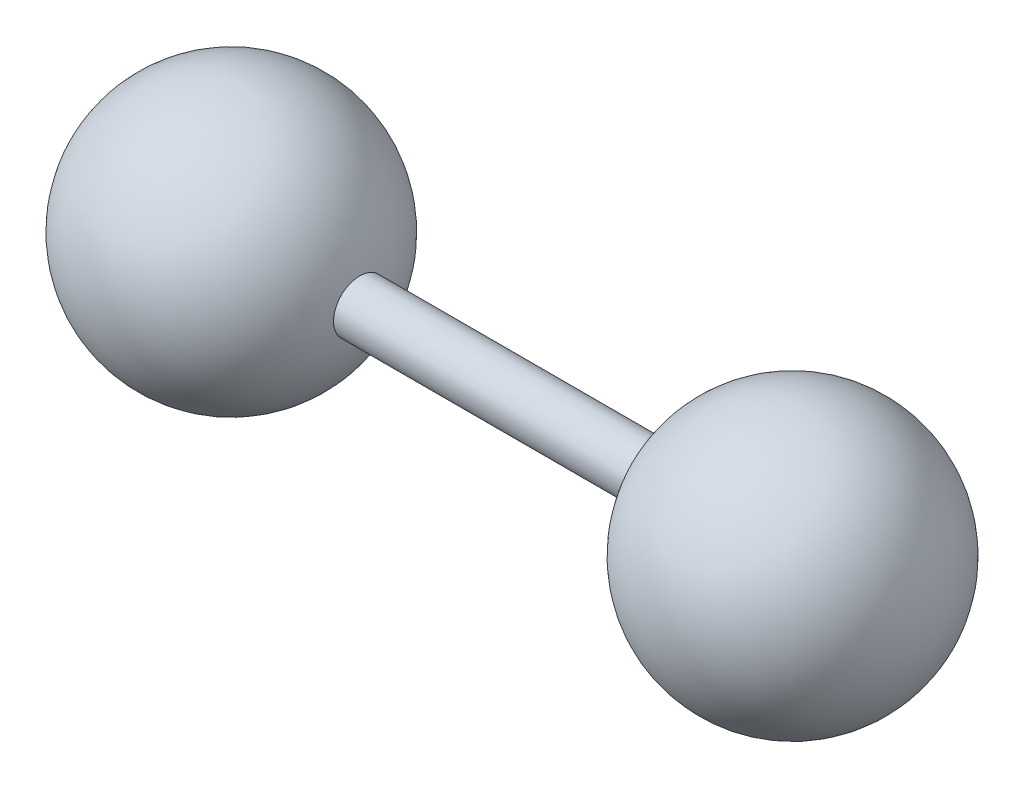
SolidWorks part; units mm, degrees
material "Wrought Stainless Steel"
ref_plane "Front Plane" through (0, 0, 0) normal (0, 0, 1) x (1, 0, 0)
ref_plane "Top Plane" through (0, 0, 0) normal (0, 1, 0) x (1, 0, 0)
ref_plane "Right Plane" through (0, 0, 0) normal (1, 0, 0) x (0, 0, -1)
sketch "Sketch1" plane through (0, 0, 0) normal (0, 0, 1) x (1, 0, 0)
  line L0 (0, 0) -> (1501.0726, 0)
  arc A0 (0, 0) -> (1501.0726, 0) centre (750.5363, 0) cw
revolve "Revolve1" add sketch "Sketch1" angle 360 about L0
sketch "Sketch3" plane through (0, 0, 0) normal (1, 0, 0) x (0, 0, -1)
  circle A0 centre (0, 0) radius 150
extrude "Boss-Extrude1" add sketch "Sketch3" along normal blind 650 and the other way blind 1800
sketch "Sketch4" plane through (0, 0, 0) normal (0, 0, 1) x (1, 0, 0)
  line L2 (-1710.6036, 0) -> (-3210.6036, 0)
  arc A3 (-1710.6036, 0) -> (-3210.6036, 0) centre (-2460.6036, 0) ccw
revolve "Revolve2" add sketch "Sketch4" angle 360 about L2
sketch "Sketch5" plane through (0, 0, 0) normal (0, 0, 1) x (1, 0, 0)
  point P5 (-2460.6036, 0)
  point P6 (750.5363, 0)
scale "Scale1" scale about centroid uniform scaling yes scale factor 0.5
ref_axis "Axis1" through (-1289.5676, 0, 0) along (1, 0, 0)
ref_axis "Axis2" through (-1289.5676, 0, 0) along (1, 0, 0)
